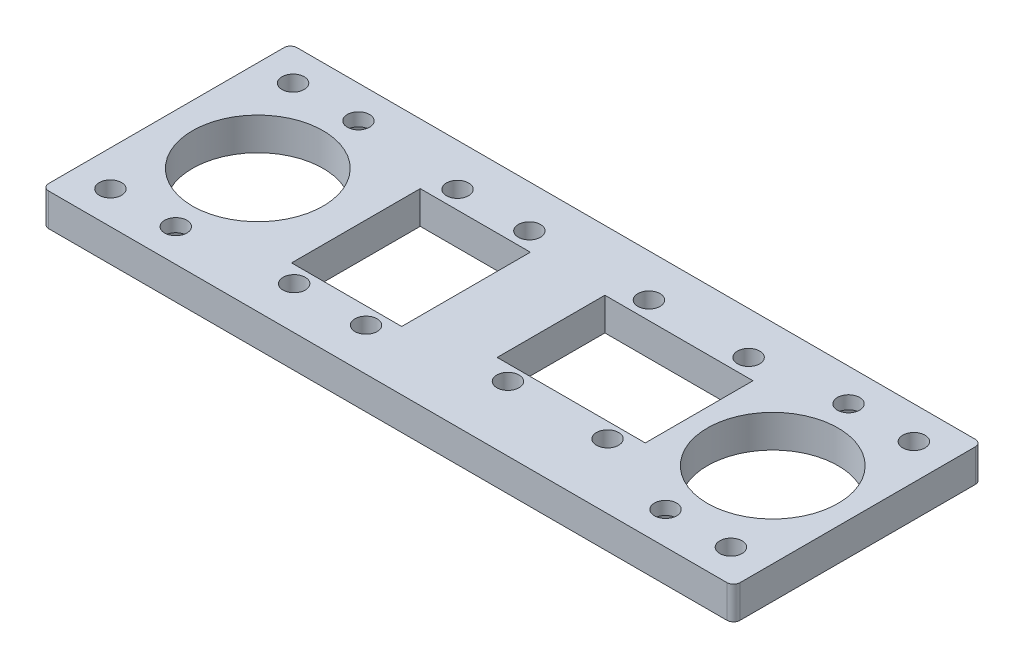
SolidWorks part; units mm, degrees
ref_plane "Front Plane" through (0, 0, 0) normal (0, 0, 1) x (1, 0, 0)
ref_plane "Top Plane" through (0, 0, 0) normal (0, 1, 0) x (1, 0, 0)
ref_plane "Right Plane" through (0, 0, 0) normal (1, 0, 0) x (0, 0, -1)
sketch "Sketch1" plane through (0, 0, 0) normal (0, 1, 0) x (1, 0, 0)
  line L1 (-52.9, 19) -> (52.9, 19)
  line L2 (-52.9, 19) -> (-52.9, -19)
  line L3 (-52.9, -19) -> (52.9, -19)
  line L4 (52.9, 19) -> (52.9, -19)
  line L5 (-23.7897, 9.7468) -> (-6.9381, 9.7468)
  line L6 (-23.7897, 9.7468) -> (-23.7897, -9.9429)
  line L7 (-23.7897, -9.9429) -> (-6.9381, -9.9429)
  line L8 (-6.9381, 9.7468) -> (-6.9381, -9.9429)
  line L9 (4.4674, 9.7468) -> (27.1321, 9.7468)
  line L10 (4.4674, 9.7468) -> (4.4674, -6.7386)
  line L11 (4.4674, -6.7386) -> (27.1321, -6.7386)
  line L12 (27.1321, 9.7468) -> (27.1321, -6.7386)
  circle A0 centre (-47.5, 14) radius 1.7
  circle A1 centre (-47.4521, -14) radius 1.7
  circle A2 centre (47.5, 14) radius 1.7
  circle A3 centre (47.5, -14) radius 1.7
  circle A4 centre (-20.8388, 12.5) radius 1.7
  circle A5 centre (-20.8388, -12.5) radius 1.7
  circle A6 centre (-9.8388, 12.5) radius 1.7
  circle A7 centre (-9.8388, -12.5) radius 1.7
  circle A8 centre (8.4683, 12.485) radius 1.7
  circle A9 centre (8.4683, -9.09) radius 1.7
  circle A10 centre (23.7083, 12.5) radius 1.7
  circle A11 centre (23.7083, -9.09) radius 1.7
  circle A12 centre (-37.5, 14) radius 1.7
  circle A13 centre (-37.4521, -14) radius 1.7
  circle A14 centre (37.5, 14) radius 1.7
  circle A15 centre (37.5, -14) radius 1.7
  circle A16 centre (-38.9, 0) radius 10
  circle A19 centre (39.9, 0) radius 10
  dimension "D3" = 28
  dimension "D4" = 95
  dimension "D5" = 105.8
  dimension "D7" = 11
  dimension "D10" = 6.5
  dimension "D13" = 10
  dimension "D18" = 75
  dimension "D19" = 52.9
  dimension "D25" = 13
  dimension "D24" = 14
  dimension "D1" = 5
  dimension "D2" = 5
  dimension "D6" = 5.4
  dimension "D8" = 25
  dimension "D9" = 6.5
  dimension "D11" = 21.59
  dimension "D12" = 15.24
  dimension "D14" = 10
  dimension "D15" = 10
  dimension "D16" = 10
  dimension "D17" = 28
  dimension "D20" = 19
  dimension "D21" = 0
  dimension "D22" = 25
  dimension "D23" = 11
extrude "Boss-Extrude3" add sketch "Sketch1" along normal blind 5
fillet "Fillet1" radius 1 4 edges at (52.9, 2.5, -19) (52.9, 2.5, 19) (-52.9, 2.5, -19) (-52.9, 2.5, 19)
sketch "Sketch2" plane through (0, 0, 0) normal (0, -1, 0) x (1, 0, 0)
  line L1 (40.6119, -14) -> (39.056, -11.305)
  line L2 (39.056, -11.305) -> (35.944, -11.305)
  line L3 (35.944, -11.305) -> (34.3881, -14)
  line L4 (34.3881, -14) -> (35.944, -16.695)
  line L5 (35.944, -16.695) -> (39.056, -16.695)
  line L6 (39.056, -16.695) -> (40.6119, -14)
  line L7 (40.6119, 14) -> (39.056, 16.695)
  line L8 (39.056, 16.695) -> (35.944, 16.695)
  line L9 (35.944, 16.695) -> (34.3881, 14)
  line L10 (34.3881, 14) -> (35.944, 11.305)
  line L11 (35.944, 11.305) -> (39.056, 11.305)
  line L12 (39.056, 11.305) -> (40.6119, 14)
  line L13 (-34.3402, 14) -> (-35.8962, 16.695)
  line L14 (-35.8962, 16.695) -> (-39.0081, 16.695)
  line L15 (-39.0081, 16.695) -> (-40.5641, 14)
  line L16 (-40.5641, 14) -> (-39.0081, 11.305)
  line L17 (-39.0081, 11.305) -> (-35.8962, 11.305)
  line L18 (-35.8962, 11.305) -> (-34.3402, 14)
  line L19 (-34.3881, -14) -> (-35.944, -11.305)
  line L20 (-35.944, -11.305) -> (-39.056, -11.305)
  line L21 (-39.056, -11.305) -> (-40.6119, -14)
  line L22 (-40.6119, -14) -> (-39.056, -16.695)
  line L23 (-39.056, -16.695) -> (-35.944, -16.695)
  line L24 (-35.944, -16.695) -> (-34.3881, -14)
  circle A0 centre (37.5, -14) radius 2.695 construction
  circle A1 centre (37.5, 14) radius 2.695 construction
  circle A2 centre (-37.4521, 14) radius 2.695 construction
  circle A3 centre (-37.5, -14) radius 2.695 construction
extrude "Cut-Extrude1" cut sketch "Sketch2" against normal blind 3
